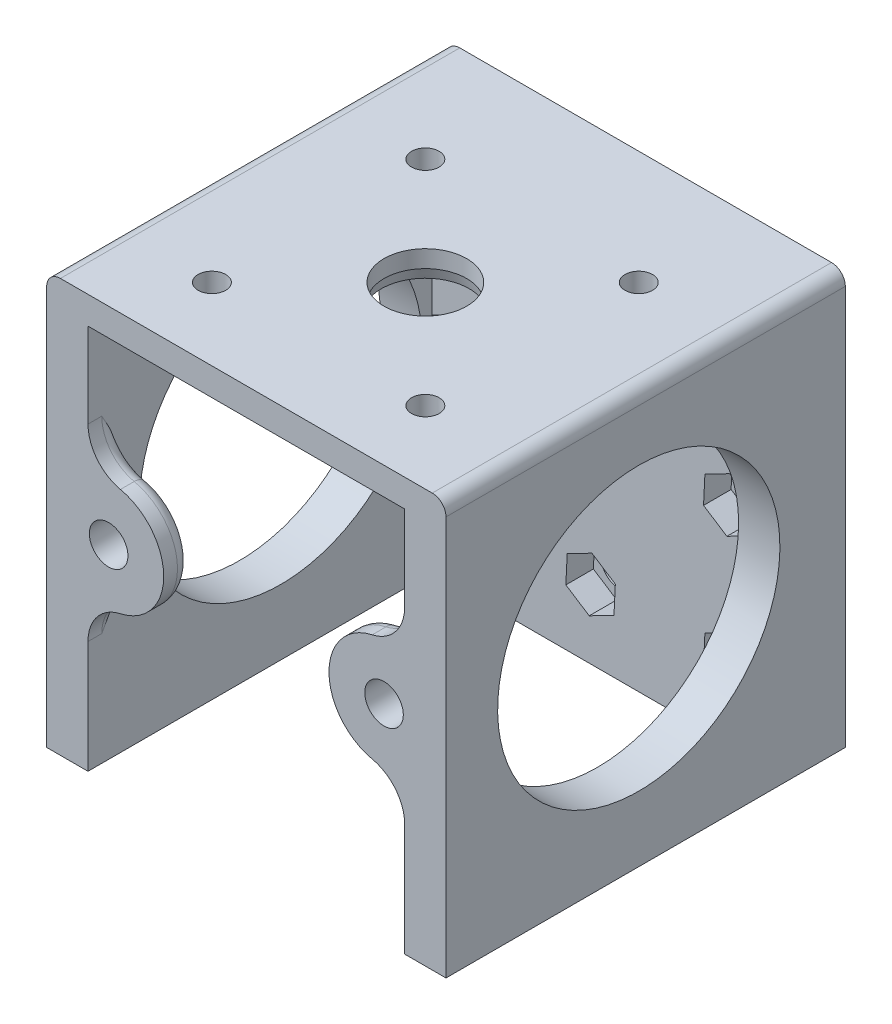
SolidWorks part; units mm, degrees
other "Markierung1"
sketch "Skizze6"
ref_plane "Ebene vorne" through (0, 0, 0) normal (0, 0, 1) x (1, 0, 0)
ref_plane "Ebene oben" through (0, 0, 0) normal (0, 1, 0) x (1, 0, 0)
ref_plane "Ebene rechts" through (0, 0, 0) normal (1, 0, 0) x (0, 0, -1)
sketch "Skizze1" plane through (0, 0, 0) normal (0, 0, 1) x (1, 0, 0)
  line L1 (-29, 0) -> (29, 0)
  line L2 (-29, 0) -> (-29, -60)
  line L3 (-29, -60) -> (29, -60)
  line L4 (29, 0) -> (29, -60)
  circle A0 centre (-20, -10) radius 2.4
  circle A1 centre (0, -10) radius 2.4
  circle A2 centre (20, -10) radius 2.4
  circle A3 centre (0, -30) radius 2.4
  circle A4 centre (20, -30) radius 2.4
  circle A5 centre (0, -50) radius 2.4
  circle A6 centre (20, -50) radius 2.4
  circle A7 centre (-20, -30) radius 2.4
  circle A8 centre (-20, -50) radius 2.4
  circle A9 centre (-10, -20) radius 1.6
  circle A10 centre (10, -20) radius 1.6
  point P4 (-29, -30)
  dimension "D4" = 0
  dimension "D1" = 58
  dimension "D2" = 29
  dimension "D3" = 60
  dimension "D5" = 3
  dimension "D6" = 3
extrude "Aufsatz-Linear austragen1" add sketch "Skizze1" along normal blind 8 contours A8 L3 A5 A6 L4 L1 L2 A7 A4 A3 A2 A1 A0 region at (0, -0.8345, 0)
sketch "Skizze4" plane through (0, 0, 8) normal (0, 0, 1) x (1, 0, 0)
  line L1 (-29, 0) -> (29, 0)
  line L2 (-29, 0) -> (-29, -59.9975)
  line L3 (-29, -59.9975) -> (29, -59.9975)
  line L4 (29, 0) -> (29, -59.9975)
  line L5 (-23, -59.9975) -> (23, -59.9975)
  line L6 (-23, -59.9975) -> (-23, -4)
  line L7 (-23, -4) -> (23, -4)
  line L8 (23, -59.9975) -> (23, -4)
  point P9 (0, -59.9975)
  line M8 (29, 0) -> (-29, 0)
  line M9 (-29, 0) -> (-29, -60)
  circle M11 centre (-20, -30) radius 2.4
  circle M12 centre (20, -30) radius 2.4
  circle M14 centre (20, -10) radius 2.4
  circle M16 centre (-20, -10) radius 2.4
  dimension "D1" = 4
  dimension "D2" = 23
  dimension "D3" = 23
  dimension "D4" = 58
extrude "Aufsatz-Linear austragen2" add sketch "Skizze4" along normal blind 50 contours L8 L3 L4 L6 L7 M8 M9 M11 M16 M14 M12 region at (0, -0.8345, 8)
sketch "Skizze5" plane through (0, 0, 0) normal (0, 1, 0) x (1, 0, 0)
  line L0 (-29, 0) -> (29, 0) construction
  line L1 (0, 0) -> (0, -64) construction
  circle A0 centre (0, -32) radius 6
  circle A1 centre (-15.5, -16.5) radius 2
  circle A2 centre (15.5, -16.5) radius 2
  circle A3 centre (15.5, -47.5) radius 2
  circle A4 centre (-15.5, -47.5) radius 2
  point P16 (0, -32)
  dimension "D1" = 32
  dimension "D2" = 15.5
  dimension "D3" = 15.5
  dimension "D4" = 2
  dimension "D5" = 2
extrude "Schnitt-Linear austragen1" cut sketch "Skizze5" against normal blind 8
sketch "Skizze10" plane through (0, 0, 58) normal (0, 0, 1) x (1, 0, 0)
  circle A0 centre (20, -30) radius 8
  circle A1 centre (-20, -30) radius 8
  circle A2 centre (-20, -30) radius 2.8
extrude "Aufsatz-Linear austragen3" add sketch "Skizze10" against normal blind 4
fillet "Verrundung1" radius 6 4 edges at (23, -37.4162, 56) (23, -22.5838, 56) (-23, -22.5838, 56) (-23, -37.4162, 56)
fillet "Verrundung3" radius 2 6 edges at (21.6752, -39.9141, 54) (12, -30, 54) (21.6752, -20.0859, 54) (-21.6752, -20.0859, 54) (-12, -30, 54) (-21.6752, -39.9141, 54)
sketch "Skizze11" plane through (0, 0, 58) normal (0, 0, 1) x (1, 0, 0)
  line L0 (29, 0) -> (-29, 0) construction
  circle A0 centre (20, -30) radius 2.8
  dimension "D1" = 30
  dimension "D2" = 20
extrude "Schnitt-Linear austragen7" cut sketch "Skizze11" against normal blind 4 contours A0
chamfer "Fase3" distance 0.4 angle 75 1 edges at (0, -4, 38) first distance on face at (-15.5, -4, 49.5)
fillet "Verrundung4" radius 2 2 edges at (-29, 0, 29) (29, 0, 29)
chamfer "Fase4" distance 4.5 angle 15 2 edges at (-8.4, -20, 0) (11.6, -20, 0) first distance on face at (-8.4, -20, 8) first distance on face at (11.6, -20, 8)
sketch "Skizze12" plane through (0, 0, 8) normal (0, 0, 1) x (1, 0, 0)
  line L1 (-16.6027, -12.189) -> (-16.4056, -8.1524)
  line L2 (-16.4056, -8.1524) -> (-19.8029, -5.9634)
  line L3 (-19.8029, -5.9634) -> (-23.3973, -7.811)
  line L4 (-23.3973, -7.811) -> (-23.5944, -11.8476)
  line L5 (-23.5944, -11.8476) -> (-20.1971, -14.0366)
  line L6 (-20.1971, -14.0366) -> (-16.6027, -12.189)
  circle A0 centre (-20, -10) radius 3.5 construction
  circle A1 centre (0, -10) radius 3.5 construction
  circle A2 centre (20, -10) radius 3.5 construction
  circle A3 centre (0, -30) radius 3.5 construction
  circle A4 centre (20, -30) radius 3.5 construction
  circle A5 centre (0, -50) radius 3.5 construction
  circle A6 centre (20, -50) radius 3.5 construction
  circle A7 centre (-20, -30) radius 3.5 construction
  circle A8 centre (-20, -50) radius 3.5 construction
  dimension "D1" = 3
  dimension "D2" = 3
extrude "Schnitt-Linear austragen8" cut sketch "Skizze12" against normal blind 4
pattern_linear "Lineares Muster1" count 3 spacing 20 along (1, 0, 0) count 3 spacing 20 along (0, -1, 0) of "Schnitt-Linear austragen8"
sketch "Skizze13" plane through (29, 0, 0) normal (1, 0, 0) x (0, 0, -1)
  circle A0 centre (-30, -30) radius 20.5
extrude "Schnitt-Linear austragen9" cut sketch "Skizze13" against normal blind 60
